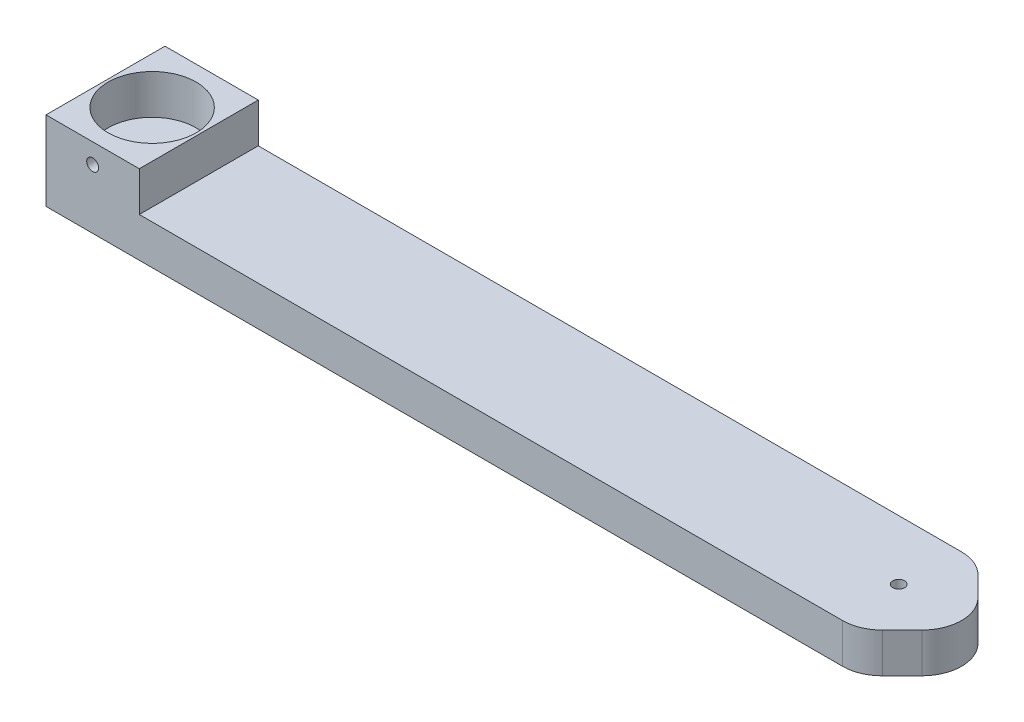
SolidWorks part; units mm, degrees
ref_plane "Front Plane" through (0, 0, 0) normal (0, 0, 1) x (1, 0, 0)
ref_plane "Top Plane" through (0, 0, 0) normal (0, 1, 0) x (1, 0, 0)
ref_plane "Right Plane" through (0, 0, 0) normal (1, 0, 0) x (0, 0, -1)
sketch "Sketch1" plane through (0, 0, 0) normal (0, 1, 0) x (1, 0, 0)
  line L1 (-110, -15) -> (110, -15)
  line L2 (-110, -15) -> (-110, 15)
  line L3 (-110, 15) -> (110, 15)
  line L4 (110, -15) -> (110, 15)
  line L5 (-110, -15) -> (110, 15) construction
  line L6 (-110, 15) -> (110, -15) construction
  point P0 (0, 0)
  dimension "D1" = 220
  dimension "D2" = 30
extrude "Boss-Extrude1" add sketch "Sketch1" along normal blind 10
sketch "Sketch2" plane through (0, 10, 0) normal (0, 1, 0) x (1, 0, 0)
  line L0 (-11, 0) -> (11, 0) construction
  line L2 (-86.4763, -15) -> (-110, -15)
  line L3 (-86.4763, -15) -> (-86.4763, 15)
  line L4 (-86.4763, 15) -> (-110, 15)
  line L5 (-110, -15) -> (-110, 15)
  line L6 (-86.4763, -15) -> (-110, 15) construction
  line L7 (-86.4763, 15) -> (-110, -15) construction
  circle A1 centre (-98.2382, 0) radius 11.1
  line M3 (110, 15) -> (-110, 15)
  line M4 (-110, 15) -> (-110, -15)
  line M5 (-110, -15) -> (110, -15)
  dimension "D2" = 22.2
extrude "Boss-Extrude3" add sketch "Sketch2" along normal blind 10 contours L3 A1 M5 M3 M4 region at (-98.2382, 10, 14.6188)
sketch "Sketch4" plane through (0, 10, 0) normal (0, 1, 0) x (1, 0, 0)
  line L0 (-11, 0) -> (11, 0) construction
  line L1 (110, -15) -> (110, 15) construction
  circle A0 centre (90, 0) radius 4
  dimension "D1" = 8
  dimension "D2" = 20
sketch "Sketch6" plane through (0, 0, 15) normal (0, 0, 1) x (1, 0, 0)
  line L0 (-86.4763, 10) -> (-110, 10) construction
  line L1 (-110, 20) -> (-110, 0) construction
  line L2 (-98.2382, 20) -> (-98.2382, 10) construction
  line L3 (-110, 20) -> (-86.4763, 20) construction
  circle A0 centre (-98.2382, 15) radius 1.5
  dimension "D1" = 3
extrude "Cut-Extrude2" cut sketch "Sketch6" against normal blind 10
extrude "Cut-Extrude3" cut sketch "Sketch4" along normal blind 4 from surface starting at face at (0, 0, 0)
sketch "Sketch7" plane through (0, 4, 0) normal (0, -1, 0) x (-1, 0, 0)
  circle A0 centre (-90, 0) radius 1.5
  dimension "D1" = 3
extrude "Cut-Extrude4" cut sketch "Sketch7" against normal blind 14
sketch "Sketch8" plane through (0, 10, 0) normal (0, 1, 0) x (1, 0, 0)
  line L0 (95, 15) -> (110, 0)
  line L1 (110, 15) -> (-86.4763, 15) construction
  line L2 (110, -15) -> (110, 15) construction
  line L4 (110, 0) -> (95, -15)
  line L5 (-86.4763, -15) -> (110, -15) construction
  line L6 (95, -15) -> (110, -15)
  line L7 (110, -15) -> (110, 0)
  line L8 (110, 0) -> (110, 15)
  line L9 (110, 15) -> (95, 15)
  line L11 (110, 15) -> (95, 15) construction
  line L12 (110, 15) -> (110, 0) construction
  line L13 (110, 0) -> (95, 0) construction
  line L14 (95, 15) -> (95, 0) construction
  line M11 (-86.4763, -15) -> (110, -15)
  line M12 (110, -15) -> (110, 15)
  line M13 (110, 15) -> (-86.4763, 15)
extrude "Cut-Extrude5" cut sketch "Sketch8" against normal blind 10 contours L4 M12 M11 | L0 M13 M12 region at (105, 10, -10) region at (105, 10, 10)
fillet "Fillet1" radius 10 3 edges at (95, 5, -15) (110, 5, 0) (95, 5, 15)
